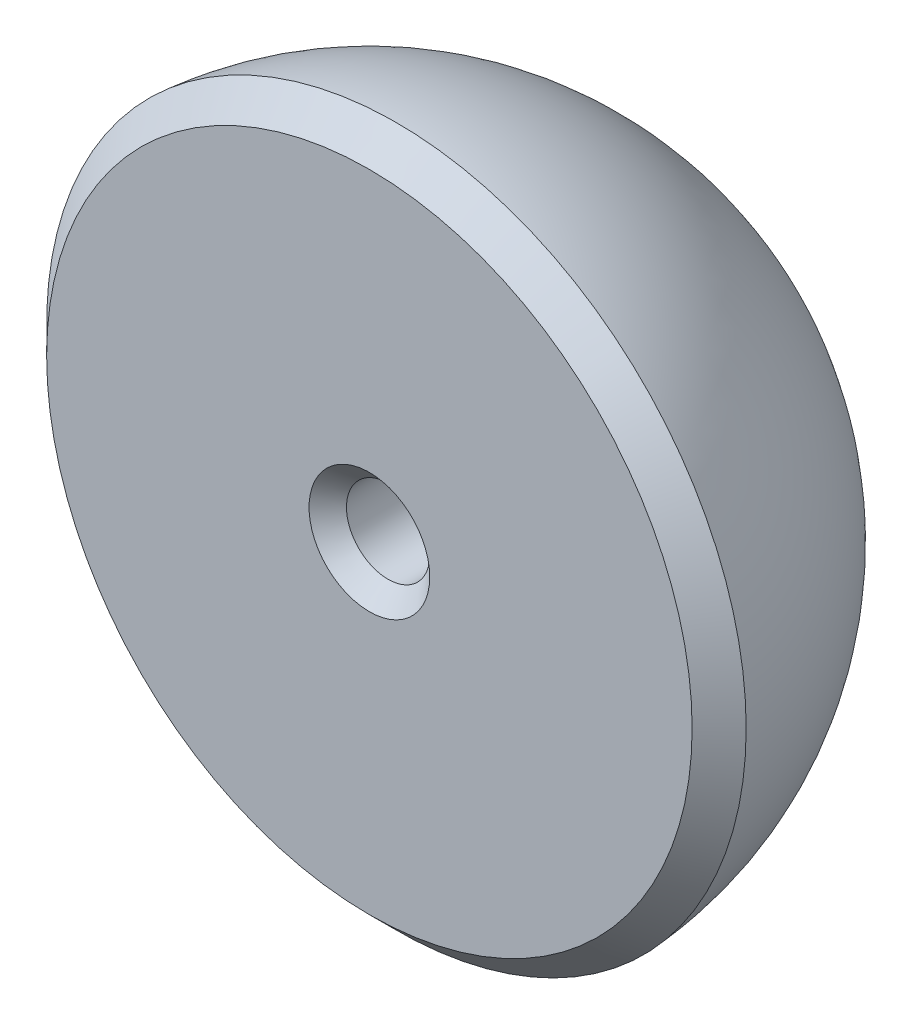
SolidWorks part; units mm, degrees
ref_plane "Front Plane" through (0, 0, 0) normal (0, 0, 1) x (1, 0, 0)
ref_plane "Top Plane" through (0, 0, 0) normal (0, 1, 0) x (1, 0, 0)
ref_plane "Right Plane" through (0, 0, 0) normal (1, 0, 0) x (0, 0, -1)
sketch "Sketch1" plane through (0, 0, 0) normal (0, 1, 0) x (1, 0, 0)
  line L0 (0, 0) -> (0, 10.9802) construction
  line L1 (0, 0) -> (0, 9.525)
  line L2 (9.525, 0) -> (0, 0)
  arc A0 (0, 9.525) -> (9.525, 0) centre (0, 0) cw
  dimension "D1" = 9.525
revolve "Revolve1" add sketch "Sketch1" angle 360 about L0
hole_wizard "#4-40 Tapped Hole1" positions "Sketch2" profile "Sketch3" tap size "#4-40" standard "ANSI Inch"
sketch "Sketch2" plane through (0, 0, 0) normal (0, 0, 1) x (1, 0, 0)
  point P0 (0, 0)
cosmetic thread "Hole Thread1" parameters "D1"=5.588, "D2"=2.8448
sketch "Sketch3" plane through (0, 0, 0) normal (1, 0, 0) x (0, -1, 0)
  line L0 (0, 0) -> (0, 7.0292)
  line L1 (0, 7.0292) -> (1.1303, 6.35)
  line L2 (1.1303, 6.35) -> (1.1303, 0)
  line L5 (1.1303, 0) -> (0, 0)
  line L10 (0, 7.0292) -> (-1.1303, 6.35) construction
  line L11 (0, -6.35) -> (0, 107.95) construction
  dimension "Tap Drill Dia." = 2.2606
  dimension "Tap Drill Depth" = 6.35
  dimension "Drill Angle" = 118
fillet "Fillet1" radius 0.7937 1 edges at (1.1303, 0, -6.35)
chamfer "Chamfer1" distance 0.762 angle 45 1 edges at (9.525, 0, 0)
chamfer "Chamfer2" distance 0.508 angle 45 1 edges at (1.1303, 0, 0)
